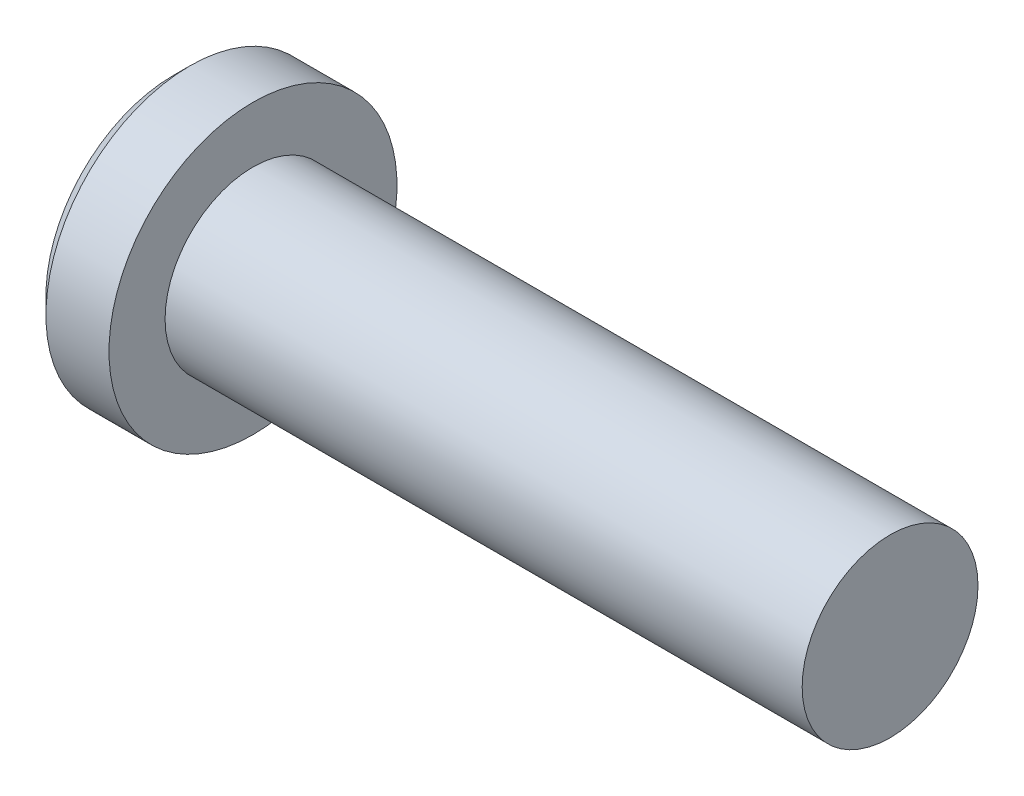
SolidWorks part; units mm, degrees
ref_plane "Front Plane" through (0, 0, 0) normal (0, 0, 1) x (1, 0, 0)
ref_plane "Top Plane" through (0, 0, 0) normal (0, 1, 0) x (1, 0, 0)
ref_plane "Right Plane" through (0, 0, 0) normal (1, 0, 0) x (0, 0, -1)
sketch "Sketch1" plane through (0, 0, 0) normal (0, 0, 1) x (1, 0, 0)
  line L0 (6.35, 0) -> (-6.35, 0) construction
  line L1 (6.35, 1.7526) -> (6.35, -1.7526) construction
  line L2 (-6.35, 2.8702) -> (-6.35, -2.8702) construction
  line L3 (-6.35, 2.8702) -> (-7.6073, 2.8702) construction
  line L4 (-7.6073, 2.8702) -> (-7.9375, 2.54) construction
  line L5 (-7.9375, 2.54) -> (-7.9375, -2.54) construction
  line L6 (-7.9375, -2.54) -> (-7.6073, -2.8702) construction
  line L7 (-7.6073, -2.8702) -> (-6.35, -2.8702) construction
  point P7 (-6.6675, 0)
  point P12 (3.175, -1.7526)
  dimension "D1" = 45
  dimension "Dec." = 3.5052
  dimension "Length" = 12.7
  dimension "Head Dia" = 5.7404
  dimension "Head Height" = 1.5875
  dimension "Hex Depth" = 1.27
  dimension "Chamfer" = 0.3302
  dimension "D2" = 3.175
ref_plane "Plane1" through (6.35, 0, 0) normal (1, 0, 0) x (0, 0, -1)
ref_plane "Plane2" through (-7.9375, 0, 0) normal (1, 0, 0) x (0, 0, -1)
sketch "Sketch2" plane through (6.35, 0, 0) normal (1, 0, 0) x (0, 0, -1)
  circle A0 centre (0, 0) radius 1.7526
extrude "Boss-Extrude1" add sketch "Sketch2" against normal up to vertex (12.7 mm away) up to point (-6.35, 0, 0)
sketch "Sketch3" plane through (6.35, 0, 0) normal (1, 0, 0) x (0, 0, -1)
  circle A0 centre (0, 0) radius 1.7526 construction
  circle A1 centre (0, 0) radius 1.7526
curve "Helix/Spiral1" pitch 0.7937 height 13.4937 turns 17 parameters "Pitch"=0.7937
chamfer "Chamfer1" [suppressed] distance 0.5953 angle 45
sketch "Sketch5" plane through (0, 0, 0) normal (0, 0, 1) x (1, 0, 0)
  line L0 (6.0027, 1.7526) -> (6.6973, 1.7526)
  line L1 (6.6973, 1.7526) -> (6.3996, 1.237)
  line L2 (6.3996, 1.237) -> (6.3004, 1.237)
  line L3 (6.3004, 1.237) -> (6.0027, 1.7526)
  line L4 (6.35, 1.237) -> (6.35, 1.7526) construction
  line L5 (6.1516, 1.4948) -> (6.5484, 1.4948) construction
  dimension "D1" = 60
  dimension "D2" = 0.3969
  dimension "D3" = 0.0992
sweep "Cut-Sweep1" [suppressed] cut profiles "Sketch5" path "Helix/Spiral1"
sketch "Sketch4" plane through (-7.9375, 0, 0) normal (1, 0, 0) x (0, 0, -1)
  line L0 (-2.8702, 0.7937) -> (2.8702, 0.7937) construction
  line L1 (0, 0.9165) -> (-0.7937, 0.4583)
  line L2 (-0.7937, 0.4583) -> (-0.7937, -0.4583)
  line L3 (-0.7937, -0.4583) -> (0, -0.9165)
  line L4 (0, -0.9165) -> (0.7937, -0.4583)
  line L5 (0.7937, -0.4583) -> (0.7937, 0.4583)
  line L6 (0.7937, 0.4583) -> (0, 0.9165)
  line L7 (0, 0) -> (0, 0.7937) construction
  circle A0 centre (0, 0) radius 0.7937 construction
  dimension "Hex Size" = 1.5875
  dimension "D1" = 5.7404
  dimension "D2" = 0.7937
sketch "Sketch6" plane through (0, 0, 0) normal (0, 0, 1) x (1, 0, 0)
  line L0 (-7.6073, 2.8702) -> (-7.9375, 2.54) construction
  line L1 (-6.35, 2.8702) -> (-7.6073, 2.8702) construction
  line L2 (-6.35, 2.8702) -> (-6.35, -2.8702) construction
  line L3 (-7.9375, 2.54) -> (-7.9375, -2.54) construction
  line L4 (-7.6073, 2.8702) -> (-7.9375, 2.54)
  line L5 (-6.35, 2.8702) -> (-7.6073, 2.8702)
  line L6 (-6.35, 2.8702) -> (-6.35, 0)
  line L7 (-7.9375, 2.54) -> (-7.9375, 0)
  line L8 (-6.35, 0) -> (-7.9375, 0) construction
  line L9 (-6.35, 0) -> (-7.9375, 0)
revolve "Revolve1" add sketch "Sketch6" angle 360 about L8
extrude "Cut-Extrude1" [suppressed] cut sketch "Sketch4" along normal up to vertex
sketch "Sketch8" plane through (-7.9375, 0, 0) normal (-1, 0, 0) x (0, 0, 1)
  circle A1 centre (0, 0) radius 0.9165
extrude "Cut-Extrude2" [suppressed] cut sketch "Sketch8" against normal through all draft 45
equation "\"D3@Helix/Spiral1\" = \"Length@Sketch1\"+\"Pitch@Helix/Spiral1\""
equation "\"D3@Sketch5\" = \"Pitch@Helix/Spiral1\"*.125"
equation "\"D2@Sketch5\" = \"Pitch@Helix/Spiral1\"*.50"
equation "\"D1@Chamfer1\" = \"Pitch@Helix/Spiral1\"*.75"
equation "\"D2@Sketch1\" = \"Pitch@Helix/Spiral1\"*4"
equation "\"D1@Sketch4\" = \"Head Dia@Sketch1\""
